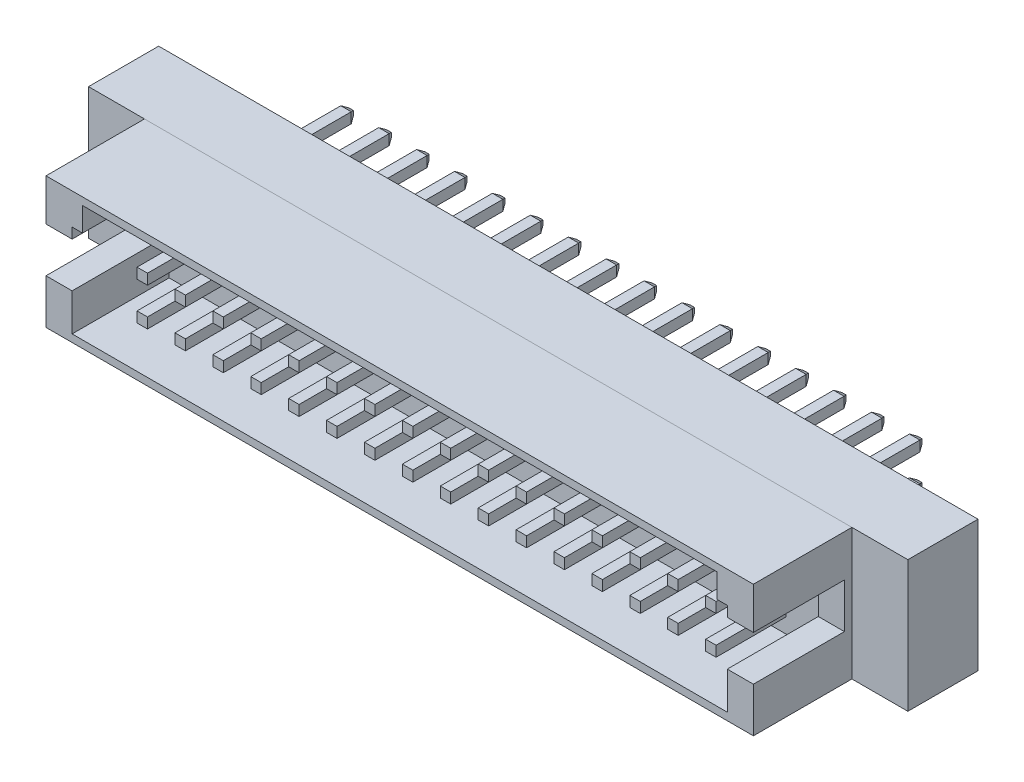
SolidWorks part; units mm, degrees
other "Детальный элемент1"
ref_plane "Спереди" through (0, 0, 0) normal (0, 0, 1) x (1, 0, 0)
ref_plane "Сверху" through (0, 0, 0) normal (0, 1, 0) x (1, 0, 0)
ref_plane "Справа" through (0, 0, 0) normal (1, 0, 0) x (0, 0, -1)
sketch "Эскиз1" plane through (0, 0, 0) normal (0, 0, 1) x (1, 0, 0)
  line L1 (-19.4, 2.89) -> (-18.7, 2.89)
  line L2 (-19.4, 2.89) -> (-19.4, 2.19)
  line L3 (-19.4, 2.19) -> (-18.7, 2.19)
  line L4 (-18.7, 2.89) -> (-18.7, 2.19)
  line L5 (-19.4, 2.89) -> (-18.7, 2.19) construction
  line L6 (-19.4, 2.19) -> (-18.7, 2.89) construction
  point P0 (-19.05, 2.54)
  dimension "D1" = 0.7
  dimension "D2" = 19.05
  dimension "D3" = 2.54
extrude "Бобышка-Вытянуть1" add sketch "Эскиз1" along normal blind 9.5 and the other way blind 4.5
chamfer "Фаска1" distance 0.2 angle 60 4 edges at (-19.4, 2.54, -4.5) (-19.05, 2.19, -4.5) (-18.7, 2.54, -4.5) (-19.05, 2.89, -4.5) first distance on face at (-19.05, 2.54, -4.5)
pattern_linear "Линейный массив1" count 3 spacing 2.54 along (0, -1, 0) count 16 spacing 2.54 along (1, 0, 0) of bodies 107
sketch "Эскиз2" plane through (0, 0, 0) normal (0, 0, 1) x (1, 0, 0)
  line L1 (27.45, 4.4) -> (-27.45, 4.4)
  line L2 (27.45, 4.4) -> (27.45, -4.4)
  line L3 (27.45, -4.4) -> (-27.45, -4.4)
  line L4 (-27.45, 4.4) -> (-27.45, -4.4)
  line L5 (27.45, 4.4) -> (-27.45, -4.4) construction
  line L6 (27.45, -4.4) -> (-27.45, 4.4) construction
  point P0 (0, 0)
  dimension "D1" = 54.9
  dimension "D2" = 8.8
extrude "Бобышка-Вытянуть2" add sketch "Эскиз2" along normal blind 4.7 separate body
sketch "Эскиз3" plane through (0, 0, 4.7) normal (0, 0, 1) x (1, 0, 0)
  line L0 (27.45, 4.4) -> (-27.45, 4.4) construction
  line L1 (-23.7, -4.4) -> (23.7, -4.4)
  line L2 (-23.7, -4.4) -> (-23.7, 4.4)
  line L3 (-23.7, 4.4) -> (23.7, 4.4)
  line L4 (23.7, -4.4) -> (23.7, 4.4)
  line L5 (-23.7, -4.4) -> (23.7, 4.4) construction
  line L6 (-23.7, 4.4) -> (23.7, -4.4) construction
  point P0 (0, 0)
  dimension "D1" = 47.4
extrude "Бобышка-Вытянуть3" add sketch "Эскиз3" along normal blind 6.6 separate body
shell "Оболочка1" thickness 0.1 removed face at (0, 0, 11.3)
sketch "Эскиз4" plane through (23.7, 0, 0) normal (1, 0, 0) x (0, 0, -1)
  line L0 (-11.3, -4.4) -> (-11.3, 4.4) construction
  line L1 (-11.3, -1.4) -> (-5.2, -1.4)
  line L2 (-11.3, -1.4) -> (-11.3, 1.6)
  line L3 (-11.3, 1.6) -> (-5.2, 1.6)
  line L4 (-5.2, -1.4) -> (-5.2, 1.6)
  line L6 (-11.3, -4.4) -> (-4.7, -4.4) construction
  line L7 (-4.7, -4.4) -> (-4.7, 4.4) construction
  point P10 (0, 0)
  dimension "D1" = 3
  dimension "D2" = 3
  dimension "D3" = 0.5
extrude "Вырез-Вытянуть2" cut sketch "Эскиз4" against normal up to surface (1.75 mm away) up to face at (21.95, 0, 8.05)
sketch "Эскиз5" plane through (21.95, 0, 0) normal (-1, 0, 0) x (0, 0, 1)
  line L0 (4.8, -3.9) -> (4.8, 3.9) construction
  line L1 (11.3, 3.9) -> (4.8, 3.9)
  line L2 (11.3, 3.9) -> (11.3, 2.3)
  line L3 (11.3, 2.3) -> (4.8, 2.3)
  line L4 (4.8, 3.9) -> (4.8, 2.3)
  dimension "D1" = 1.6
extrude "Бобышка-Вытянуть4" add sketch "Эскиз5" along normal blind 0.7
mirror "Зеркальное отражение1" about plane through (0, 0, 0) normal (1, 0, 0) of "Бобышка-Вытянуть4", "Вырез-Вытянуть2"
